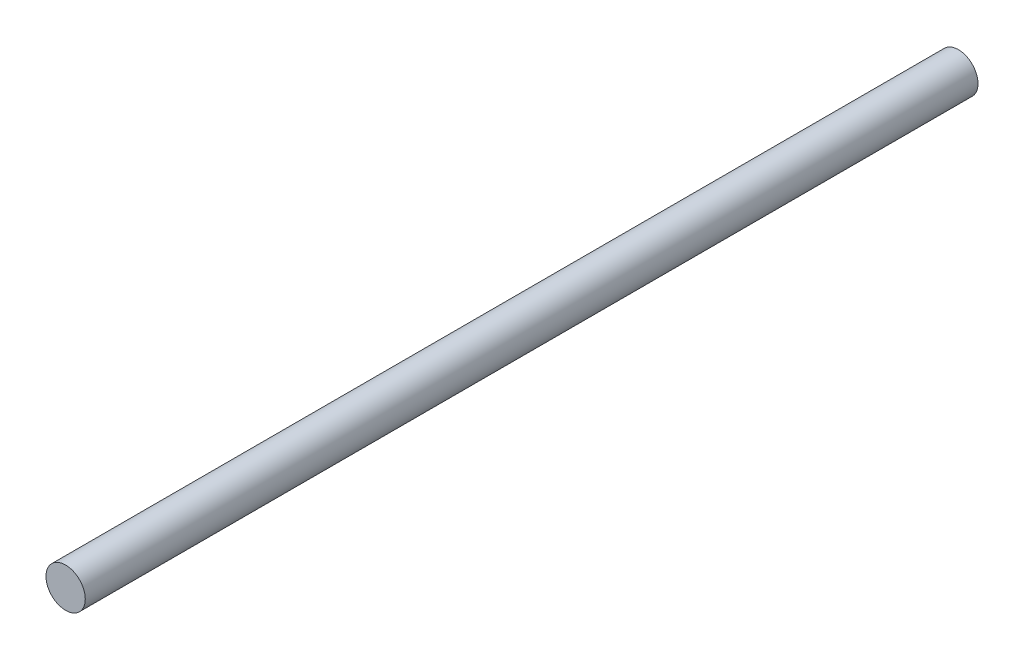
SolidWorks part; units mm, degrees
material "Plain Carbon Steel"
ref_plane "Front Plane" through (0, 0, 0) normal (0, 0, 1) x (1, 0, 0)
ref_plane "Top Plane" through (0, 0, 0) normal (0, 1, 0) x (1, 0, 0)
ref_plane "Right Plane" through (0, 0, 0) normal (1, 0, 0) x (0, 0, -1)
sketch "Sketch1" plane through (0, 0, 0) normal (0, 0, 1) x (1, 0, 0)
  circle A0 centre (0, 0) radius 1.9844
  dimension "D1" = 3.9688
extrude "Boss-Extrude1" add sketch "Sketch1" along normal blind 90.1253
